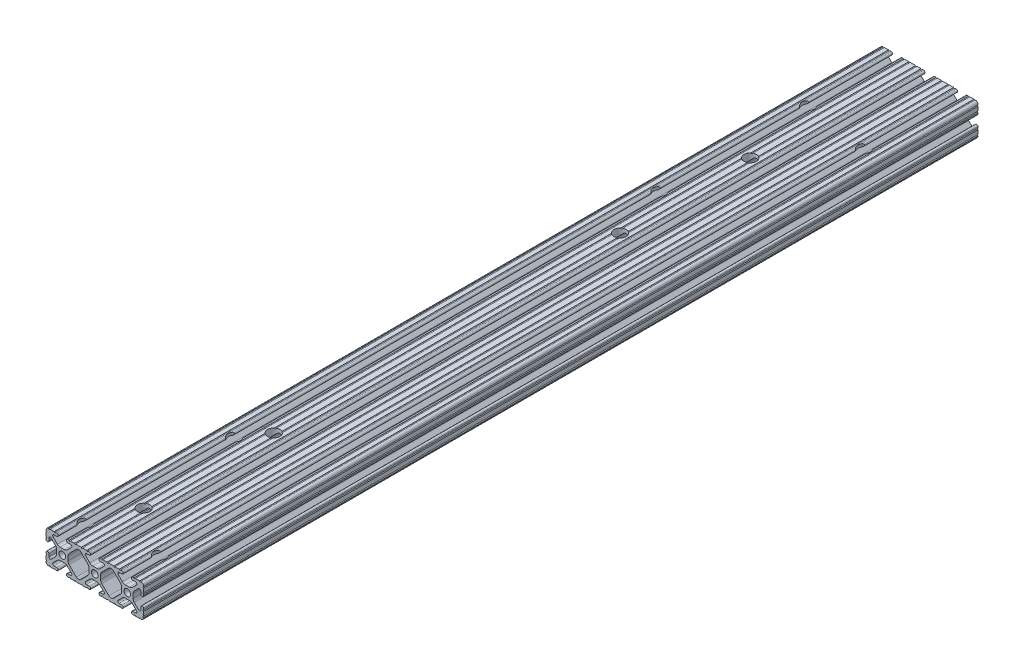
SolidWorks part; units mm, degrees
material "McMaster 6061-T6"
ref_plane "Front Plane" through (0, 0, 0) normal (0, 0, 1) x (1, 0, 0)
ref_plane "Top Plane" through (0, 0, 0) normal (0, 1, 0) x (1, 0, 0)
ref_plane "Right Plane" through (0, 0, 0) normal (1, 0, 0) x (0, 0, -1)
sketch "Sketch1" plane through (0, 0, 0) normal (0, 0, 1) x (1, 0, 0)
  line B0 (12.1463, -9.9314) -> (13.2537, -9.9314)
  line B1 (5.4384, -3.8759) -> (11.0327, -9.4702)
  line B2 (4.5085, 1.6308) -> (4.5085, -1.6308)
  line B3 (11.0327, 9.4702) -> (5.4384, 3.8759)
  line B4 (13.2537, 9.9314) -> (12.1463, 9.9314)
  line B5 (19.9616, 3.8759) -> (14.3673, 9.4702)
  line B6 (20.8915, -1.6308) -> (20.8915, 1.6308)
  line B7 (14.3673, -9.4702) -> (19.9616, -3.8759)
  line B8 (-13.2537, -9.9314) -> (-12.1463, -9.9314)
  line B9 (-19.9616, -3.8759) -> (-14.3673, -9.4702)
  line B10 (-20.8915, 1.6308) -> (-20.8915, -1.6308)
  line B11 (-14.3673, 9.4702) -> (-19.9616, 3.8759)
  line B12 (-12.1463, 9.9314) -> (-13.2537, 9.9314)
  line B13 (-5.4384, 3.8759) -> (-11.0327, 9.4702)
  line B14 (-4.5085, -1.6308) -> (-4.5085, 1.6308)
  line B15 (-11.0327, -9.4702) -> (-5.4384, -3.8759)
  line B16 (-34.9504, -12.7) -> (-31.7246, -12.7)
  line B17 (-30.7086, -12.7) -> (-29.7023, -12.7)
  line B18 (-29.7023, -10.4902) -> (-31.8748, -10.4902)
  line B19 (-32.5932, -8.7558) -> (-29.2759, -5.4384)
  line B20 (-27.0308, -4.5085) -> (-23.7692, -4.5085)
  line B21 (-21.5241, -5.4384) -> (-18.2068, -8.7558)
  line B22 (-18.9252, -10.4902) -> (-21.0977, -10.4902)
  line B23 (-21.0977, -12.7) -> (-20.0914, -12.7)
  line B24 (-19.0754, -12.7) -> (-15.8496, -12.7)
  line B25 (-14.8336, -12.7) -> (-10.5664, -12.7)
  line B26 (-9.5504, -12.7) -> (-6.3246, -12.7)
  line B27 (-5.3086, -12.7) -> (-4.3023, -12.7)
  line B28 (-4.3023, -10.4902) -> (-6.4748, -10.4902)
  line B29 (-7.1932, -8.7558) -> (-3.8759, -5.4384)
  line B30 (-1.6308, -4.5085) -> (1.6308, -4.5085)
  line B31 (3.8759, -5.4384) -> (7.1932, -8.7558)
  line B32 (6.4748, -10.4902) -> (4.3023, -10.4902)
  line B33 (4.3023, -12.7) -> (5.3086, -12.7)
  line B34 (6.3246, -12.7) -> (9.5504, -12.7)
  line B35 (10.5664, -12.7) -> (14.8336, -12.7)
  line B36 (15.8496, -12.7) -> (19.0754, -12.7)
  line B37 (20.0914, -12.7) -> (21.0977, -12.7)
  line B38 (21.0977, -10.4902) -> (18.9252, -10.4902)
  line B39 (18.2068, -8.7558) -> (21.5241, -5.4384)
  line B40 (23.7692, -4.5085) -> (27.0308, -4.5085)
  line B41 (29.2759, -5.4384) -> (32.5932, -8.7558)
  line B42 (31.8748, -10.4902) -> (29.7023, -10.4902)
  line B43 (29.7023, -12.7) -> (30.7086, -12.7)
  line B44 (31.7246, -12.7) -> (34.9504, -12.7)
  line B45 (38.1, -9.5504) -> (38.1, -6.3246)
  line B46 (38.1, -5.3086) -> (38.1, -4.3023)
  line B47 (35.8902, -4.3023) -> (35.8902, -6.4748)
  line B48 (34.1558, -7.1932) -> (30.8384, -3.8759)
  line B49 (29.9085, -1.6308) -> (29.9085, 1.6308)
  line B50 (30.8384, 3.8759) -> (34.1558, 7.1932)
  line B51 (35.8902, 6.4748) -> (35.8902, 4.3023)
  line B52 (38.1, 4.3023) -> (38.1, 5.3086)
  line B53 (38.1, 6.3246) -> (38.1, 9.5504)
  line B54 (34.9504, 12.7) -> (31.7246, 12.7)
  line B55 (30.7086, 12.7) -> (29.7023, 12.7)
  line B56 (29.7023, 10.4902) -> (31.8748, 10.4902)
  line B57 (32.5932, 8.7558) -> (29.2759, 5.4384)
  line B58 (27.0308, 4.5085) -> (23.7692, 4.5085)
  line B59 (21.5241, 5.4384) -> (18.2068, 8.7558)
  line B60 (18.9252, 10.4902) -> (21.0977, 10.4902)
  line B61 (21.0977, 12.7) -> (20.0914, 12.7)
  line B62 (19.0754, 12.7) -> (15.8496, 12.7)
  line B63 (14.8336, 12.7) -> (10.5664, 12.7)
  line B64 (9.5504, 12.7) -> (6.3246, 12.7)
  line B65 (5.3086, 12.7) -> (4.3023, 12.7)
  line B66 (4.3023, 10.4902) -> (6.4748, 10.4902)
  line B67 (7.1932, 8.7558) -> (3.8759, 5.4384)
  line B68 (1.6308, 4.5085) -> (-1.6308, 4.5085)
  line B69 (-3.8759, 5.4384) -> (-7.1932, 8.7558)
  line B70 (-6.4748, 10.4902) -> (-4.3023, 10.4902)
  line B71 (-4.3023, 12.7) -> (-5.3086, 12.7)
  line B72 (-6.3246, 12.7) -> (-9.5504, 12.7)
  line B73 (-10.5664, 12.7) -> (-14.8336, 12.7)
  line B74 (-15.8496, 12.7) -> (-19.0754, 12.7)
  line B75 (-20.0914, 12.7) -> (-21.0977, 12.7)
  line B76 (-21.0977, 10.4902) -> (-18.9252, 10.4902)
  line B77 (-18.2068, 8.7558) -> (-21.5241, 5.4384)
  line B78 (-23.7692, 4.5085) -> (-27.0308, 4.5085)
  line B79 (-29.2759, 5.4384) -> (-32.5932, 8.7558)
  line B80 (-31.8748, 10.4902) -> (-29.7023, 10.4902)
  line B81 (-29.7023, 12.7) -> (-30.7086, 12.7)
  line B82 (-31.7246, 12.7) -> (-34.9504, 12.7)
  line B83 (-38.1, 9.5504) -> (-38.1, 6.3246)
  line B84 (-38.1, 5.3086) -> (-38.1, 4.3023)
  line B85 (-35.8902, 4.3023) -> (-35.8902, 6.4748)
  line B86 (-34.1558, 7.1932) -> (-30.8384, 3.8759)
  line B87 (-29.9085, 1.6308) -> (-29.9085, -1.6308)
  line B88 (-30.8384, -3.8759) -> (-34.1558, -7.1932)
  line B89 (-35.8902, -6.4748) -> (-35.8902, -4.3023)
  line B90 (-38.1, -4.3023) -> (-38.1, -5.3086)
  line B91 (-38.1, -6.3246) -> (-38.1, -9.5504)
  circle B92 centre (25.4, 0) radius 2.6035
  circle B93 centre (0, 0) radius 2.6035
  circle B94 centre (-25.4, 0) radius 2.6035
  arc B95 (13.2537, -9.9314) -> (14.3673, -9.4702) centre (13.2537, -8.3566) ccw
  arc B96 (11.0327, -9.4702) -> (12.1463, -9.9314) centre (12.1463, -8.3566) ccw
  arc B97 (4.5085, -1.6308) -> (5.4384, -3.8759) centre (7.6835, -1.6308) ccw
  arc B98 (5.4384, 3.8759) -> (4.5085, 1.6308) centre (7.6835, 1.6308) ccw
  arc B99 (12.1463, 9.9314) -> (11.0327, 9.4702) centre (12.1463, 8.3566) ccw
  arc B100 (14.3673, 9.4702) -> (13.2537, 9.9314) centre (13.2537, 8.3566) ccw
  arc B101 (20.8915, 1.6308) -> (19.9616, 3.8759) centre (17.7165, 1.6308) ccw
  arc B102 (19.9616, -3.8759) -> (20.8915, -1.6308) centre (17.7165, -1.6308) ccw
  arc B103 (-12.1463, -9.9314) -> (-11.0327, -9.4702) centre (-12.1463, -8.3566) ccw
  arc B104 (-14.3673, -9.4702) -> (-13.2537, -9.9314) centre (-13.2537, -8.3566) ccw
  arc B105 (-20.8915, -1.6308) -> (-19.9616, -3.8759) centre (-17.7165, -1.6308) ccw
  arc B106 (-19.9616, 3.8759) -> (-20.8915, 1.6308) centre (-17.7165, 1.6308) ccw
  arc B107 (-13.2537, 9.9314) -> (-14.3673, 9.4702) centre (-13.2537, 8.3566) ccw
  arc B108 (-11.0327, 9.4702) -> (-12.1463, 9.9314) centre (-12.1463, 8.3566) ccw
  arc B109 (-4.5085, 1.6308) -> (-5.4384, 3.8759) centre (-7.6835, 1.6308) ccw
  arc B110 (-5.4384, -3.8759) -> (-4.5085, -1.6308) centre (-7.6835, -1.6308) ccw
  arc B111 (-38.1, -10.5664) -> (-35.9664, -12.7) centre (-35.992, -10.592) ccw
  arc B112 (-34.9504, -12.7) -> (-35.9664, -12.7) centre (-35.4584, -12.7) ccw
  arc B113 (-30.7086, -12.7) -> (-31.7246, -12.7) centre (-31.2166, -12.7) ccw
  arc B114 (-29.7023, -12.7) -> (-29.7023, -10.4902) centre (-29.7023, -11.5951) ccw
  arc B115 (-32.5932, -8.7558) -> (-31.8748, -10.4902) centre (-31.8748, -9.4742) ccw
  arc B116 (-27.0308, -4.5085) -> (-29.2759, -5.4384) centre (-27.0308, -7.6835) ccw
  arc B117 (-21.5241, -5.4384) -> (-23.7692, -4.5085) centre (-23.7692, -7.6835) ccw
  arc B118 (-18.9252, -10.4902) -> (-18.2068, -8.7558) centre (-18.9252, -9.4742) ccw
  arc B119 (-21.0977, -10.4902) -> (-21.0977, -12.7) centre (-21.0977, -11.5951) ccw
  arc B120 (-19.0754, -12.7) -> (-20.0914, -12.7) centre (-19.5834, -12.7) ccw
  arc B121 (-14.8336, -12.7) -> (-15.8496, -12.7) centre (-15.3416, -12.7) ccw
  arc B122 (-9.5504, -12.7) -> (-10.5664, -12.7) centre (-10.0584, -12.7) ccw
  arc B123 (-5.3086, -12.7) -> (-6.3246, -12.7) centre (-5.8166, -12.7) ccw
  arc B124 (-4.3023, -12.7) -> (-4.3023, -10.4902) centre (-4.3023, -11.5951) ccw
  arc B125 (-7.1932, -8.7558) -> (-6.4748, -10.4902) centre (-6.4748, -9.4742) ccw
  arc B126 (-1.6308, -4.5085) -> (-3.8759, -5.4384) centre (-1.6308, -7.6835) ccw
  arc B127 (3.8759, -5.4384) -> (1.6308, -4.5085) centre (1.6308, -7.6835) ccw
  arc B128 (6.4748, -10.4902) -> (7.1932, -8.7558) centre (6.4748, -9.4742) ccw
  arc B129 (4.3023, -10.4902) -> (4.3023, -12.7) centre (4.3023, -11.5951) ccw
  arc B130 (6.3246, -12.7) -> (5.3086, -12.7) centre (5.8166, -12.7) ccw
  arc B131 (10.5664, -12.7) -> (9.5504, -12.7) centre (10.0584, -12.7) ccw
  arc B132 (15.8496, -12.7) -> (14.8336, -12.7) centre (15.3416, -12.7) ccw
  arc B133 (20.0914, -12.7) -> (19.0754, -12.7) centre (19.5834, -12.7) ccw
  arc B134 (21.0977, -12.7) -> (21.0977, -10.4902) centre (21.0977, -11.5951) ccw
  arc B135 (18.2068, -8.7558) -> (18.9252, -10.4902) centre (18.9252, -9.4742) ccw
  arc B136 (23.7692, -4.5085) -> (21.5241, -5.4384) centre (23.7692, -7.6835) ccw
  arc B137 (29.2759, -5.4384) -> (27.0308, -4.5085) centre (27.0308, -7.6835) ccw
  arc B138 (31.8748, -10.4902) -> (32.5932, -8.7558) centre (31.8748, -9.4742) ccw
  arc B139 (29.7023, -10.4902) -> (29.7023, -12.7) centre (29.7023, -11.5951) ccw
  arc B140 (31.7246, -12.7) -> (30.7086, -12.7) centre (31.2166, -12.7) ccw
  arc B141 (35.9664, -12.7) -> (34.9504, -12.7) centre (35.4584, -12.7) ccw
  arc B142 (35.9664, -12.7) -> (38.1, -10.5664) centre (35.992, -10.592) ccw
  arc B143 (38.1, -9.5504) -> (38.1, -10.5664) centre (38.1, -10.0584) ccw
  arc B144 (38.1, -5.3086) -> (38.1, -6.3246) centre (38.1, -5.8166) ccw
  arc B145 (38.1, -4.3023) -> (35.8902, -4.3023) centre (36.9951, -4.3023) ccw
  arc B146 (34.1558, -7.1932) -> (35.8902, -6.4748) centre (34.8742, -6.4748) ccw
  arc B147 (29.9085, -1.6308) -> (30.8384, -3.8759) centre (33.0835, -1.6308) ccw
  arc B148 (30.8384, 3.8759) -> (29.9085, 1.6308) centre (33.0835, 1.6308) ccw
  arc B149 (35.8902, 6.4748) -> (34.1558, 7.1932) centre (34.8742, 6.4748) ccw
  arc B150 (35.8902, 4.3023) -> (38.1, 4.3023) centre (36.9951, 4.3023) ccw
  arc B151 (38.1, 6.3246) -> (38.1, 5.3086) centre (38.1, 5.8166) ccw
  arc B152 (38.1, 10.5664) -> (38.1, 9.5504) centre (38.1, 10.0584) ccw
  arc B153 (38.1, 10.5664) -> (35.9664, 12.7) centre (35.992, 10.592) ccw
  arc B154 (34.9504, 12.7) -> (35.9664, 12.7) centre (35.4584, 12.7) ccw
  arc B155 (30.7086, 12.7) -> (31.7246, 12.7) centre (31.2166, 12.7) ccw
  arc B156 (29.7023, 12.7) -> (29.7023, 10.4902) centre (29.7023, 11.5951) ccw
  arc B157 (32.5932, 8.7558) -> (31.8748, 10.4902) centre (31.8748, 9.4742) ccw
  arc B158 (27.0308, 4.5085) -> (29.2759, 5.4384) centre (27.0308, 7.6835) ccw
  arc B159 (21.5241, 5.4384) -> (23.7692, 4.5085) centre (23.7692, 7.6835) ccw
  arc B160 (18.9252, 10.4902) -> (18.2068, 8.7558) centre (18.9252, 9.4742) ccw
  arc B161 (21.0977, 10.4902) -> (21.0977, 12.7) centre (21.0977, 11.5951) ccw
  arc B162 (19.0754, 12.7) -> (20.0914, 12.7) centre (19.5834, 12.7) ccw
  arc B163 (14.8336, 12.7) -> (15.8496, 12.7) centre (15.3416, 12.7) ccw
  arc B164 (9.5504, 12.7) -> (10.5664, 12.7) centre (10.0584, 12.7) ccw
  arc B165 (5.3086, 12.7) -> (6.3246, 12.7) centre (5.8166, 12.7) ccw
  arc B166 (4.3023, 12.7) -> (4.3023, 10.4902) centre (4.3023, 11.5951) ccw
  arc B167 (7.1932, 8.7558) -> (6.4748, 10.4902) centre (6.4748, 9.4742) ccw
  arc B168 (1.6308, 4.5085) -> (3.8759, 5.4384) centre (1.6308, 7.6835) ccw
  arc B169 (-3.8759, 5.4384) -> (-1.6308, 4.5085) centre (-1.6308, 7.6835) ccw
  arc B170 (-6.4748, 10.4902) -> (-7.1932, 8.7558) centre (-6.4748, 9.4742) ccw
  arc B171 (-4.3023, 10.4902) -> (-4.3023, 12.7) centre (-4.3023, 11.5951) ccw
  arc B172 (-6.3246, 12.7) -> (-5.3086, 12.7) centre (-5.8166, 12.7) ccw
  arc B173 (-10.5664, 12.7) -> (-9.5504, 12.7) centre (-10.0584, 12.7) ccw
  arc B174 (-15.8496, 12.7) -> (-14.8336, 12.7) centre (-15.3416, 12.7) ccw
  arc B175 (-20.0914, 12.7) -> (-19.0754, 12.7) centre (-19.5834, 12.7) ccw
  arc B176 (-21.0977, 12.7) -> (-21.0977, 10.4902) centre (-21.0977, 11.5951) ccw
  arc B177 (-18.2068, 8.7558) -> (-18.9252, 10.4902) centre (-18.9252, 9.4742) ccw
  arc B178 (-23.7692, 4.5085) -> (-21.5241, 5.4384) centre (-23.7692, 7.6835) ccw
  arc B179 (-29.2759, 5.4384) -> (-27.0308, 4.5085) centre (-27.0308, 7.6835) ccw
  arc B180 (-31.8748, 10.4902) -> (-32.5932, 8.7558) centre (-31.8748, 9.4742) ccw
  arc B181 (-29.7023, 10.4902) -> (-29.7023, 12.7) centre (-29.7023, 11.5951) ccw
  arc B182 (-31.7246, 12.7) -> (-30.7086, 12.7) centre (-31.2166, 12.7) ccw
  arc B183 (-35.9664, 12.7) -> (-34.9504, 12.7) centre (-35.4584, 12.7) ccw
  arc B184 (-35.9664, 12.7) -> (-38.1, 10.5664) centre (-35.992, 10.592) ccw
  arc B185 (-38.1, 9.5504) -> (-38.1, 10.5664) centre (-38.1, 10.0584) ccw
  arc B186 (-38.1, 5.3086) -> (-38.1, 6.3246) centre (-38.1, 5.8166) ccw
  arc B187 (-38.1, 4.3023) -> (-35.8902, 4.3023) centre (-36.9951, 4.3023) ccw
  arc B188 (-34.1558, 7.1932) -> (-35.8902, 6.4748) centre (-34.8742, 6.4748) ccw
  arc B189 (-29.9085, 1.6308) -> (-30.8384, 3.8759) centre (-33.0835, 1.6308) ccw
  arc B190 (-30.8384, -3.8759) -> (-29.9085, -1.6308) centre (-33.0835, -1.6308) ccw
  arc B191 (-35.8902, -6.4748) -> (-34.1558, -7.1932) centre (-34.8742, -6.4748) ccw
  arc B192 (-35.8902, -4.3023) -> (-38.1, -4.3023) centre (-36.9951, -4.3023) ccw
  arc B193 (-38.1, -6.3246) -> (-38.1, -5.3086) centre (-38.1, -5.8166) ccw
  arc B194 (-38.1, -10.5664) -> (-38.1, -9.5504) centre (-38.1, -10.0584) ccw
sketch_block_instance "Block-8020 1x3-1"
sketch_block "Block-8020 1x3"
extrude "Boss-Extrude1" add sketch "Sketch1" against normal up to surface (651.3605 mm away)
hole_wizard "CBORE for 1/4 Binding Head Machine Screw1" positions "Sketch2" profile "Sketch3" counterbore size "1/4" standard "ANSI Inch" end condition through all
sketch "Sketch2" plane through (0, 12.7, 0) normal (0, 1, 0) x (1, 0, 0)
  point P0 (-25.4, 582.3995)
  point P3 (25.4, 575.1605)
  point P6 (-25.4, 466.3215)
  point P9 (25.4, 25.4)
  point P12 (-25.4, 18.161)
  point P15 (-25.4, 134.239)
sketch "Sketch3" plane through (-25.4, 12.7, -582.3995) normal (1, 0, 0) x (0, 0, 1)
  line L0 (0, 0) -> (0, 25.4002)
  line L1 (0, 25.4002) -> (3.3782, 25.4002)
  line L3 (3.3782, 25.4002) -> (3.3782, 6.35)
  line L4 (3.3782, 6.35) -> (4.7625, 6.35)
  line L5 (4.7625, 6.35) -> (4.7625, 0)
  line L7 (4.7625, 0) -> (0, 0)
  line L11 (0, -6.35) -> (0, 107.95) construction
  dimension "Thru Hole Dia." = 6.7564
  dimension "Thru Hole Depth" = 25.4002
  dimension "C'Bore Dia." = 9.525
  dimension "C'Bore Depth" = 6.35
hole_wizard "1/4 (0.25) Diameter Hole1" positions "Sketch4" profile "Sketch5" hole size "1/4" standard "ANSI Inch" end condition through all
sketch "Sketch4" plane through (0, -12.7, 0) normal (0, -1, 0) x (-1, 0, 0)
  point P0 (25.4, 613.2605)
  point P3 (0, 613.2605)
  point P6 (0, 638.6605)
  point P9 (25.4, 638.6605)
sketch "Sketch5" plane through (-25.4, -12.7, -613.2605) normal (1, 0, 0) x (0, 0, -1)
  line L0 (0, 0) -> (0, 25.4002)
  line L1 (0, 25.4002) -> (3.175, 25.4002)
  line L2 (3.175, 25.4002) -> (3.175, 0)
  line L5 (3.175, 0) -> (0, 0)
  line L11 (0, -6.35) -> (0, 107.95) construction
  dimension "Thru Hole Dia." = 6.35
  dimension "Thru Hole Depth" = 25.4002
hole_wizard "3/8 (0.375) Diameter Hole1" positions "Sketch6" profile "Sketch7" hole size "3/8" standard "ANSI Inch" end condition through all
sketch "Sketch6" plane through (0, -12.7, 0) normal (0, -1, 0) x (-1, 0, 0)
  point P0 (12.7, 524.3605)
  point P3 (12.7, 422.7605)
  point P6 (12.7, 50.8)
  point P9 (12.7, 152.4)
sketch "Sketch7" plane through (-12.7, -12.7, -524.3605) normal (1, 0, 0) x (0, 0, -1)
  line L0 (0, 0) -> (0, 25.4002)
  line L1 (0, 25.4002) -> (4.7625, 25.4002)
  line L2 (4.7625, 25.4002) -> (4.7625, 0)
  line L5 (4.7625, 0) -> (0, 0)
  line L11 (0, -6.35) -> (0, 107.95) construction
  dimension "Thru Hole Dia." = 9.525
  dimension "Thru Hole Depth" = 25.4002
sketch "Sketch8" plane through (0, 0, -651.3605) normal (0, 0, -1) x (-1, 0, 0)
  line L1 (-38.1, 12.7) -> (38.1, 12.7)
  line L2 (-38.1, 12.7) -> (-38.1, -12.7)
  line L3 (-38.1, -12.7) -> (38.1, -12.7)
  line L4 (38.1, 12.7) -> (38.1, -12.7)
  line L5 (-49.5346, 26.3817) -> (48.6865, 26.3817)
  line L6 (-49.5346, 26.3817) -> (-49.5346, -26.7518)
  line L7 (-49.5346, -26.7518) -> (48.6865, -26.7518)
  line L8 (48.6865, 26.3817) -> (48.6865, -26.7518)
extrude "Cut-Extrude1" cut sketch "Sketch8" against normal through all both and the other way through all
